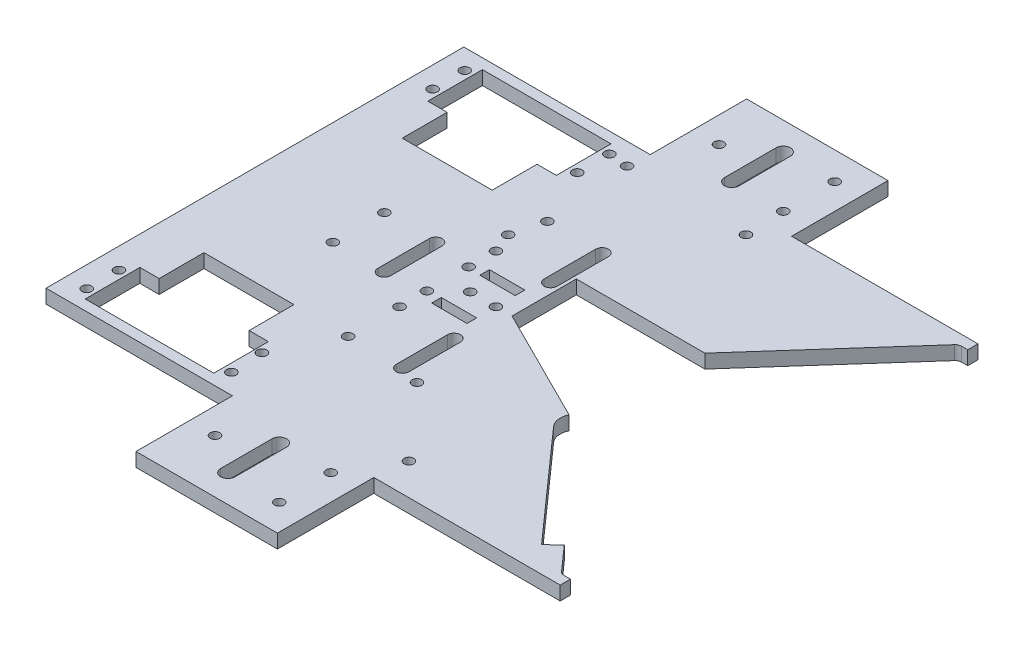
SolidWorks part; units mm, degrees
ref_plane "Front Plane" through (0, 0, 0) normal (0, 0, 1) x (1, 0, 0)
ref_plane "Top Plane" through (0, 0, 0) normal (0, 1, 0) x (1, 0, 0)
ref_plane "Right Plane" through (0, 0, 0) normal (1, 0, 0) x (0, 0, -1)
sketch "Sketch2" plane through (0, 0, 0) normal (0, 1, 0) x (1, 0, 0)
  line L2 (0, 0) -> (0, 65)
  line L3 (0, 65) -> (58, 65)
  line L4 (160, 0) -> (160, 65)
  line L8 (0, 0) -> (160, 0)
  line L9 (102, 65) -> (160, 65)
  line L11 (102, 65) -> (102, 95)
  line L12 (58, 65) -> (58, 95)
  line L13 (58, 95) -> (102, 95)
  dimension "D1" = 65
  dimension "D2" = 160
  dimension "D3" = 44
  dimension "D4" = 30
extrude "Boss-Extrude1" add sketch "Sketch2" along normal blind 4.3
mirror "Mirror1" about plane through (0, 4.3, 0) normal (0, 0, -1) of bodies 101
sketch "Sketch3" plane through (0, 4.3, 0) normal (0, 1, 0) x (1, 0, 0)
  line L0 (160, 61.8) -> (160, -61.8)
  line L1 (120.0126, 20) -> (157.1565, 61.8)
  line L3 (80.0126, 0) -> (80.0126, 20)
  line L4 (80.0126, 20) -> (120.0126, 20)
  line L12 (160, 65) -> (102, 65)
  line L13 (102, 65) -> (102, 95)
  line L15 (102, 95) -> (58, 95)
  line L16 (58, 65) -> (0, 65)
  line L17 (0, 65) -> (0, -65)
  line L18 (0, -65) -> (58, -65)
  line L20 (58, 95) -> (58, 65)
  line L22 (102, -65) -> (160, -65)
  line L23 (160, -65) -> (160, 65)
  line L36 (58, -65) -> (58, -95)
  line L38 (58, -95) -> (102, -95)
  line L39 (58, -95) -> (102, -95)
  line L40 (102, -95) -> (102, -65)
  line L42 (160, -61.8) -> (157.1556, -61.8)
  line L45 (160, 61.8) -> (157.1565, 61.8)
  line L48 (80.0126, 0) -> (120, -20)
  line L49 (120, -20) -> (157.1556, -61.8)
  line M24 (160, -65) -> (160, 65)
  dimension "D2" = 130
  dimension "D3" = 20
  dimension "D4" = 40
  dimension "D1" = 0
extrude "Cut-Extrude1" cut sketch "Sketch3" against normal blind 4.5 contours L48 L49 L1 L4 L3 M24 region at (132.7054, 4.3, -1.1594)
fillet "Fillet1" radius 2 2 edges at (157.1565, 2.15, -61.8) (157.1556, 2.15, 61.8)
ref_axis "Axis1" through (80, 4.3, 95) along (0, 0, -1)
sketch "Sketch4" plane through (0, 4.3, 0) normal (0, 1, 0) x (1, 0, 0)
  line L0 (80, -95) -> (80, 95)
  line L1 (102, -95) -> (58, -95) construction
  line L2 (102, 95) -> (58, 95) construction
ref_plane "Plane2" through (0, 4.3, 0) normal (0, 1, 0) x (1, 0, 0)
sketch "Sketch6" plane through (0, 4.3, 0) normal (0, 1, 0) x (1, 0, 0)
  line L3 (9, -61.8) -> (49, -61.8)
  line L6 (29, -45.8) -> (29, -44.8)
  line L7 (9, -44.8) -> (15, -44.8)
  line L11 (43, -44.8) -> (43, -30.8418)
  line L12 (15, -44.8) -> (15, -30.8418)
  line L13 (15, -30.8418) -> (43, -30.8418)
  line L15 (0, 0) -> (80.0126, 0)
  line L16 (80.0126, 0) -> (120, -20) construction
  line L18 (9, 44.8) -> (15, 44.8)
  line L20 (15, 30.8418) -> (43, 30.8418)
  line L21 (15, 44.8) -> (15, 30.8418)
  line L22 (43, 44.8) -> (43, 30.8418)
  line L25 (15, -45.8) -> (15, -30.8418) construction
  line L27 (9, 61.8) -> (49, 61.8)
  line L30 (4, -61.8) -> (3, -61.8)
  line L31 (0, -61.8) -> (160, -61.8) construction
  line L32 (3, -61.8) -> (4, -61.8)
  line L33 (3, -44.8) -> (3, -62.8) construction
  line L34 (3, -62.8) -> (55, -62.8) construction
  line L35 (55, -44.8) -> (55, -62.8) construction
  line L36 (4, -61.8) -> (54, -61.8) construction
  line L37 (0, 61.8) -> (160, 61.8) construction
  line L38 (54, 61.8) -> (55, 61.8)
  line L39 (54, 61.8) -> (55, 61.8)
  line L40 (43, 44.8) -> (49, 44.8)
  line L41 (4, -45.8) -> (4, -61.8) construction
  line L42 (4, -45.8) -> (54, -45.8) construction
  line L43 (43, -44.8) -> (49, -44.8)
  line L44 (3, -44.8) -> (55, -44.8) construction
  line L45 (29, -45.8) -> (29, -30.8418) construction
  line L46 (43, -45.8) -> (43, -30.8418) construction
  line L47 (54, -45.8) -> (54, -61.8) construction
  line L48 (9, -61.8) -> (49, -61.8)
  line L52 (9, 61.8) -> (9, 44.8)
  line L53 (55, 61.8) -> (54, 61.8)
  line L56 (49, 61.8) -> (49, 44.8)
  line L59 (3, -61.8) -> (4, -61.8)
  line L60 (9, -44.8) -> (9, -61.8)
  line L64 (49, -44.8) -> (49, -61.8)
  dimension "D4" = 1
  dimension "D5" = 14
  dimension "D6" = 14
extrude "Cut-Extrude2" cut sketch "Sketch6" against normal blind 10
sketch "Sketch8" plane through (0, 4.3, 0) normal (0, 1, 0) x (1, 0, 0)
  circle A0 centre (6.5, 58.8) radius 1.5
  circle A1 centre (6.5, 48.8) radius 1.5
  circle A2 centre (51.5, 48.8) radius 1.5
  circle A3 centre (51.5, 58.8) radius 1.5
  circle A4 centre (6.5, -48.8) radius 1.5
  circle A5 centre (6.5, -58.8) radius 1.5
  circle A6 centre (51.5, -58.8) radius 1.5
  circle A7 centre (51, -48.8) radius 1.5
  dimension "D7" = 3
extrude "Cut-Extrude3" cut sketch "Sketch8" against normal blind 10
sketch "Sketch9" plane through (0, 0, 0) normal (0, -1, 0) x (1, 0, 0)
  line L0 (75.75, 70.4) -> (75.75, 86.4)
  line L1 (75.75, -86.4) -> (75.75, -70.4)
  line L2 (80.25, -86.4) -> (80.25, -70.4)
  line L4 (80.25, 70.4) -> (80.25, 86.4)
  circle A0 centre (94, 70.4) radius 1.5
  circle A1 centre (66, 78.4) radius 1.5
  circle A2 centre (66, -78.4) radius 1.5
  circle A3 centre (94, -86.4) radius 1.5
  circle A4 centre (94, 86.4) radius 1.5
  circle A5 centre (94, -70.4) radius 1.5
  arc A6 (75.75, -86.4) -> (80.25, -86.4) centre (78, -86.4) ccw
  arc A7 (80.25, -70.4) -> (75.75, -70.4) centre (78, -70.4) ccw
  arc A10 (75.75, 70.4) -> (80.25, 70.4) centre (78, 70.4) ccw
  arc A12 (80.25, 86.4) -> (75.75, 86.4) centre (78, 86.4) ccw
  dimension "D1" = 3
extrude "Cut-Extrude4" cut sketch "Sketch9" against normal blind 10
sketch "Sketch7" plane through (0, 4.3, 0) normal (0, 1, 0) x (1, 0, 0)
  line L0 (0, 0) -> (80.0126, 0)
  line L1 (0, 65) -> (0, -65) construction
  line L2 (80.0126, 0) -> (80.0126, 20) construction
  line L3 (80, -95) -> (80, 95) construction
  line L4 (64, -9) -> (75, -9)
  line L5 (64, -6) -> (75, -6)
  line L6 (64, -9) -> (64, -6)
  line L7 (75, -9) -> (75, -6)
  line L8 (64, -7.5) -> (75, -7.5)
  line L9 (64, 7.5) -> (75, 7.5)
  line L10 (75, 9) -> (75, 6)
  line L11 (64, 9) -> (64, 6)
  line L12 (64, 6) -> (75, 6)
  line L13 (64, 9) -> (75, 9)
  circle A0 centre (60.0126, -6.5) radius 1.5
  circle A1 centre (60.0126, 6.5) radius 1.5
  dimension "D1" = 3
  dimension "D2" = 6.5
  dimension "D3" = 20
  dimension "D6" = 11
  dimension "D4" = 5
  dimension "D5" = 3
  dimension "D7" = 7.5
sketch "Sketch10" plane through (0, 4.3, 0) normal (0, 1, 0) x (1, 0, 0)
  line L0 (120, -20) -> (156.5589, -61.1287) construction
  line L1 (123.3218, -23.737) -> (149.8964, -53.6334)
  line L2 (116.263, -23.3218) -> (146.1593, -56.9552)
  line L3 (149.8964, -53.6334) -> (146.1593, -56.9552)
  line L4 (120, -20) -> (156.5589, -61.1287) construction
  line L5 (116.263, -23.3218) -> (152.8218, -64.4505) construction
  arc A0 (123.3218, -23.737) -> (116.263, -23.3218) centre (120, -20) ccw
  dimension "D1" = 5
  dimension "D2" = 45
extrude "Cut-Extrude5" cut sketch "Sketch10" against normal blind 10
sketch "Sketch11" plane through (0, 0, 0) normal (0, -1, 0) x (1, 0, 0)
  line L0 (0, 0) -> (80.0126, 0) construction
  line L1 (80, 95) -> (80, -95) construction
  line L2 (80.0126, 0) -> (0, 0)
  line L4 (75, 31.0313) -> (75, 15.0313)
  line L6 (79, 31.0313) -> (79, 15.0313)
  line L7 (79, -31.0313) -> (79, -15.0313)
  line L8 (75, -31.0313) -> (75, -15.0313)
  circle A0 centre (60, 31) radius 1.5
  circle A1 centre (60, 15) radius 1.5
  arc A2 (75, 31.0313) -> (79, 31.0313) centre (77, 31.0313) cw
  arc A3 (75, 15.0313) -> (79, 15.0313) centre (77, 15.0313) ccw
  arc A4 (75, -15.0313) -> (79, -15.0313) centre (77, -15.0313) cw
  arc A5 (75, -31.0313) -> (79, -31.0313) centre (77, -31.0313) ccw
  circle A6 centre (60, -15) radius 1.5
  circle A7 centre (60, -31) radius 1.5
  dimension "D1" = 3
  dimension "D2" = 16
  dimension "D3" = 15
  dimension "D4" = 20
  dimension "D5" = 15
  dimension "D6" = 4
extrude "Cut-Extrude6" cut sketch "Sketch11" against normal blind 10 contours L4 A3 L6 A2 | L8 A5 L7 A4 | A7 | A0 | A1 | A6 region at (77, 0, 23.0313) region at (77, 0, -23.0313) region at (60, 0, -31)
sketch "Sketch12" plane through (0, 0, 0) normal (0, -1, 0) x (-1, 0, 0)
  line L0 (0, 0) -> (-80.0126, 0) construction
  line L3 (-50.2627, -8) -> (-50.2627, 8)
  line L4 (-50.2627, 0) -> (-46.2627, 0)
  line L5 (-46.2627, -8) -> (-46.2627, 8)
  circle A0 centre (-32.2627, -8) radius 1.5
  circle A1 centre (-32.2627, 8) radius 1.5
  arc A2 (-46.2627, 8) -> (-50.2627, 8) centre (-48.2627, 8) ccw
  arc A3 (-50.2627, -8) -> (-46.2627, -8) centre (-48.2627, -8) ccw
  dimension "D1" = 3
  dimension "D2" = 8
  dimension "D3" = 14
  dimension "D4" = 4
extrude "Cut-Extrude7" cut sketch "Sketch12" against normal blind 10 contours A3 L5 L4 L3 | L4 L5 A2 L3 | A0 | A1 region at (48.2627, 0, 4.7958) region at (48.2627, 0, -4.7958) region at (32.2627, 0, 8) region at (32.2627, 0, -8)
extrude "Cut-Extrude8" cut sketch "Sketch7" against normal blind 9 contours A0 | L4 L7 L5 L6 | L12 L10 L13 L11 | A1
sketch "Sketch13" plane through (0, 4.3, 0) normal (0, 1, 0) x (1, 0, 0)
  line L0 (80.0126, 0) -> (59.0194, 0)
  line L1 (80, -95) -> (80, 95) construction
  circle A0 centre (67, 0) radius 1.5
  circle A1 centre (75, 0) radius 1.5
  dimension "D2" = 3
  dimension "D3" = 5
  dimension "D1" = 8
extrude "Cut-Extrude9" cut sketch "Sketch13" against normal blind 10 contours L0 A0 | L0 A0 | L0 A1 | L0 A1 region at (75, 4.3, 0.6366) region at (75, 4.3, -0.6366) region at (67, 4.3, 0.6366) region at (67, 4.3, -0.6366)
sketch "Sketch14" plane through (0, 4.3, 0) normal (0, 1, 0) x (1, 0, 0)
  circle A0 centre (57.5, 58.3) radius 1.5
  circle A1 centre (94.5, 58.3) radius 1.5
  circle A2 centre (57.5, 21.3) radius 1.5
  circle A3 centre (83.1278, -32.706) radius 1.5
  circle A4 centre (103.0587, -55.1282) radius 1.5
  dimension "D1" = 3
  dimension "D2" = 3
extrude "Cut-Extrude10" cut sketch "Sketch14" against normal blind 10
